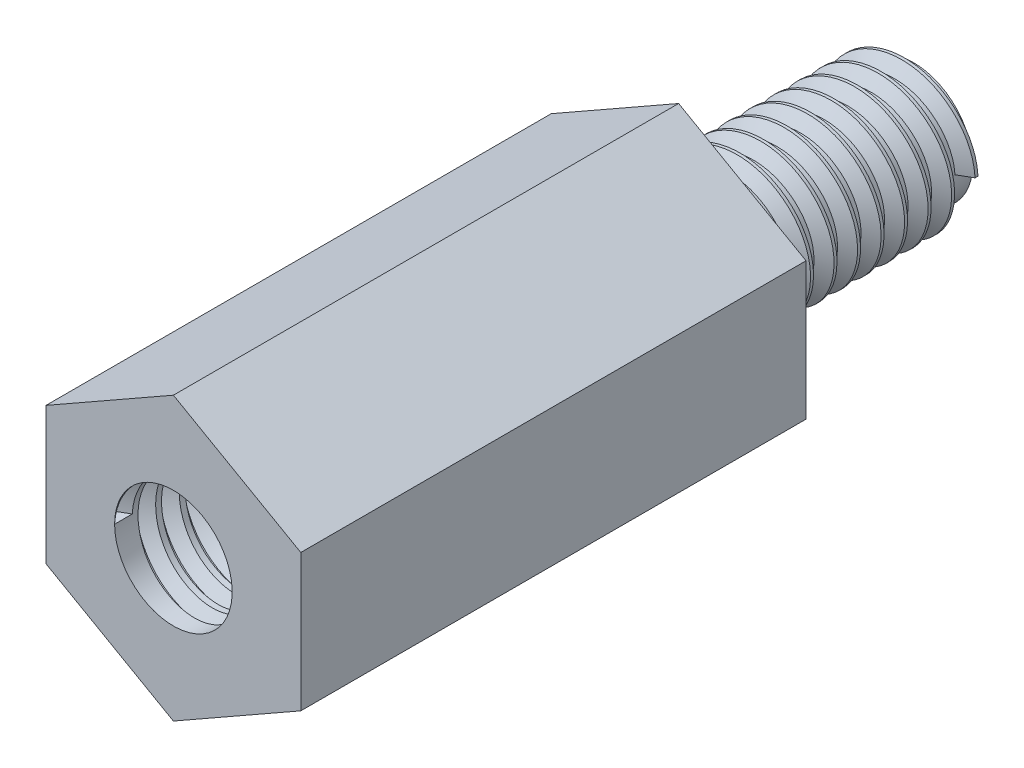
SolidWorks part; units mm, degrees
material "1.4000 (X6Cr13)"
ref_plane "Plan de face" through (0, 0, 0) normal (0, 0, 1) x (1, 0, 0)
ref_plane "Plan de dessus" through (0, 0, 0) normal (0, 1, 0) x (1, 0, 0)
ref_plane "Plan de droite" through (0, 0, 0) normal (1, 0, 0) x (0, 0, -1)
sketch "Esquisse1" plane through (0, 0, 0) normal (0, 0, 1) x (1, 0, 0)
  line L0 (-3.25, 0) -> (3.25, 0) construction
  line L1 (0, 3.6) -> (0, -3.6) construction
  line L2 (-3.25, 1.75) -> (-3.25, -1.75)
  line L3 (0, 3.6) -> (-3.25, 1.75)
  line L4 (-3.25, -1.75) -> (0, -3.6)
  line L5 (3.25, 1.75) -> (3.25, -1.75)
  line L6 (3.25, -1.75) -> (0, -3.6)
  line L7 (0, 3.6) -> (3.25, 1.75)
  point P4 (0, 0)
  point P6 (0, 0)
  point P9 (-3.25, 0)
  dimension "D1" = 6.5
  dimension "D2" = 7.2
  dimension "D3" = 3.5
extrude "Boss.-Extru.1" add sketch "Esquisse1" along normal blind 12.89
sketch "Esquisse2" plane through (0, 0, 12.89) normal (0, 0, 1) x (1, 0, 0)
  circle A0 centre (0, 0) radius 1.5
  dimension "D1" = 3
extrude "Enlèv. mat.-Extru.1" cut sketch "Esquisse2" against normal blind 6
sketch "Esquisse3" plane through (0, 0, 0) normal (0, 0, -1) x (-1, 0, 0)
  circle A0 centre (0, 0) radius 1.5
  dimension "D1" = 3
extrude "Boss.-Extru.2" add sketch "Esquisse3" along normal blind 6
thread "Filetage1" pitch 0.6 method extrude profile "Profil de filetage1" start angle 0, offset 0, length 5, pitch 0.6, diameter 3
ref_plane "Plan1" through (1.5, 0, -6) normal (0, -1, 0) x (1, 0, 0)
sketch "Profil de filetage1" plane through (1.5, 0, -6) normal (0, -1, 0) x (1, 0, 0)
  line L0 (0, 0) -> (0, 0.6) construction
  line L1 (0, 0) -> (0.3248, 0.1875)
  line L2 (0.3248, 0.1875) -> (0.3248, 0.2625)
  line L3 (0.3248, 0.2625) -> (0, 0.45)
  line L4 (0.3248, 0.225) -> (0, 0.225) construction
  line L11 (0, 0) -> (0, 0.45)
  point P2 (0, 0)
  dimension "Pitch" = 0.6
  dimension "Profile_Angle" = 60
  dimension "Profile_Land" = 0.075
  dimension "Profile_Height" = 0.3248
thread "Filetage2" pitch 0.6 method cut profile "Profil de filetage2" start angle 0, offset 0, length 0, pitch 0.6, diameter 3
ref_plane "Plan2" through (-1.5, 0, 12.89) normal (0, -1, 0) x (-1, 0, 0)
sketch "Profil de filetage2" plane through (-1.5, 0, 12.89) normal (0, -1, 0) x (-1, 0, 0)
  line L0 (0, 0) -> (0, 0.6) construction
  line L1 (0, 0) -> (0.3248, 0.1875)
  line L2 (0.3248, 0.1875) -> (0.3248, 0.2625)
  line L3 (0.3248, 0.2625) -> (0, 0.45)
  line L4 (0.3248, 0.225) -> (0, 0.225) construction
  line L11 (0, 0) -> (0, 0.45)
  point P2 (0, 0)
  dimension "Pitch" = 0.6
  dimension "Profile_Angle" = 60
  dimension "Profile_Land" = 0.075
  dimension "Profile_Height" = 0.3248
